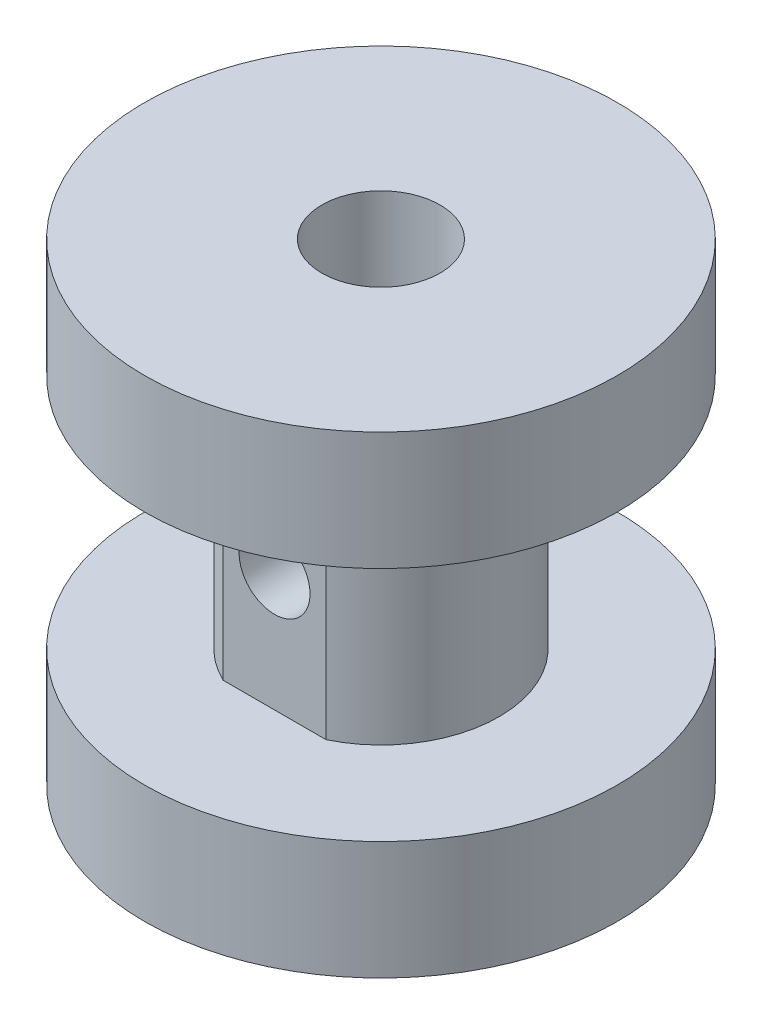
SolidWorks part; units mm, degrees
ref_plane "Front Plane" through (0, 0, 0) normal (0, 0, 1) x (1, 0, 0)
ref_plane "Top Plane" through (0, 0, 0) normal (0, 1, 0) x (1, 0, 0)
ref_plane "Right Plane" through (0, 0, 0) normal (1, 0, 0) x (0, 0, -1)
sketch "Sketch1" plane through (0, 0, 0) normal (0, 1, 0) x (1, 0, 0)
  line L0 (-2.1794, -4.5) -> (2.1794, -4.5)
  circle A0 centre (0, 0) radius 10
  circle A1 centre (0, 0) radius 5
  circle A2 centre (0, 0) radius 2.5
  dimension "D1" = 20
  dimension "D2" = 10
  dimension "D3" = 5
  dimension "D4" = 4.5
extrude "Boss-Extrude1" add sketch "Sketch1" along normal mid plane 20 contours A0 A1 | A1 A2 | L0 A1 region at (-2.5822, 0, -4.1197) region at (0, 0, 4.7009) region at (-9.7172, 0, 0)
extrude "Cut-Extrude1" cut sketch "Sketch1<3>" against normal mid plane 10 contours A0 A1 | L0 A1 region at (0, 0, 4.7009) region at (-9.7172, 0, 0)
sketch "Sketch1<3>" plane through (0, 0, 0) normal (0, 1, 0) x (1, 0, 0) same geometry as "Sketch1"
sketch "Sketch4" plane through (0, 0, 4.5) normal (0, 0, 1) x (1, 0, 0)
  circle A0 centre (0, 0) radius 1.5
  dimension "D1" = 3
extrude "Cut-Extrude2" cut sketch "Sketch4" against normal up to next
